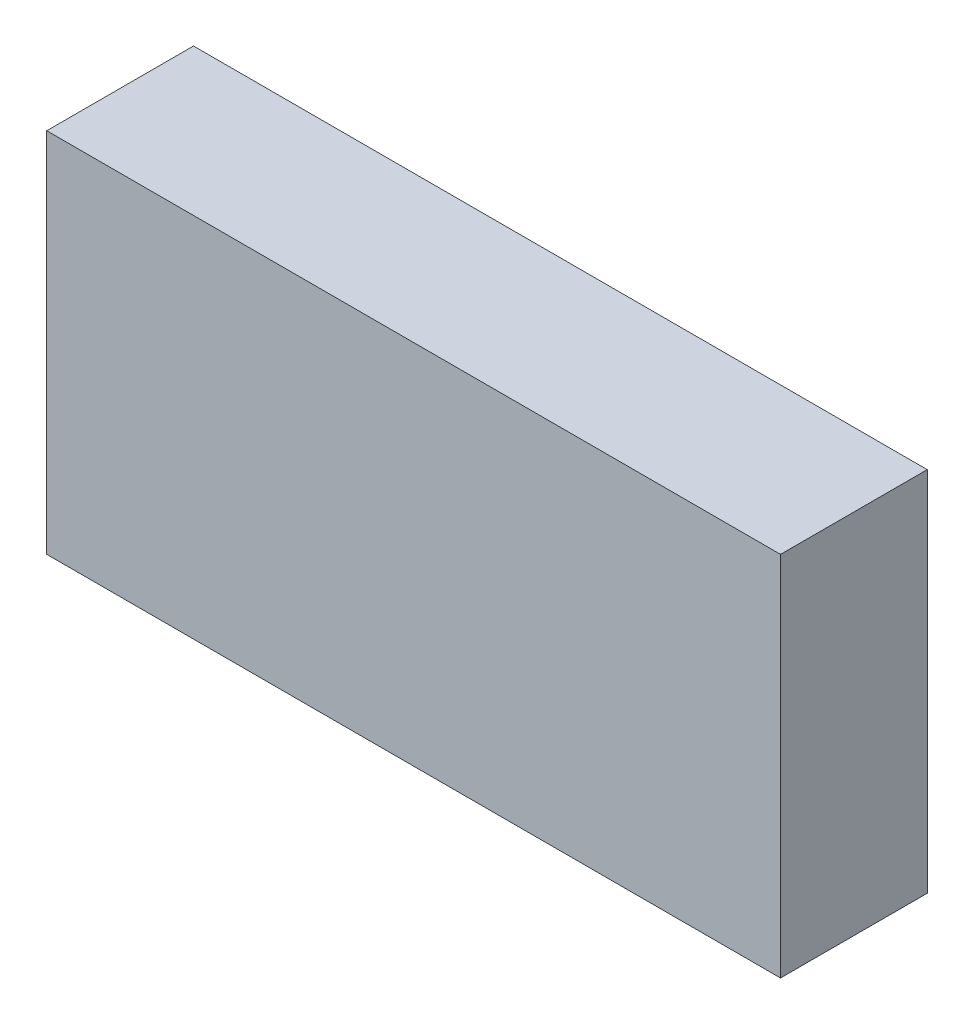
SolidWorks part; units mm, degrees
ref_plane "Front Plane" through (0, 0, 0) normal (0, 0, 1) x (1, 0, 0)
ref_plane "Top Plane" through (0, 0, 0) normal (0, 1, 0) x (1, 0, 0)
ref_plane "Right Plane" through (0, 0, 0) normal (1, 0, 0) x (0, 0, -1)
sketch "Sketch1" plane through (0, 0, 0) normal (0, 1, 0) x (1, 0, 0)
  line L1 (0, 0) -> (200, 0)
  line L2 (0, 0) -> (0, 40)
  line L3 (0, 40) -> (200, 40)
  line L4 (200, 0) -> (200, 40)
  dimension "D1" = 40
  dimension "D2" = 200
extrude "Boss-Extrude1" add sketch "Sketch1" along normal blind 100
